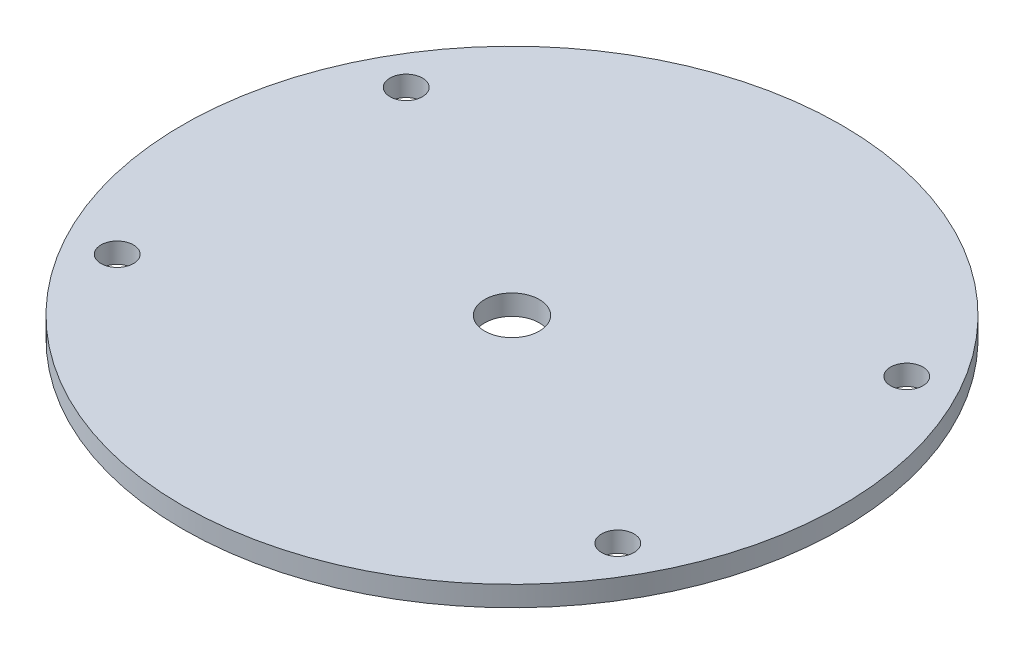
SolidWorks part; units mm, degrees
ref_plane "前视基准面" through (0, 0, 0) normal (0, 0, 1) x (1, 0, 0)
ref_plane "上视基准面" through (0, 0, 0) normal (0, 1, 0) x (1, 0, 0)
ref_plane "右视基准面" through (0, 0, 0) normal (1, 0, 0) x (0, 0, -1)
sketch "草图1" plane through (0, 0, 0) normal (0, 1, 0) x (1, 0, 0)
  line L0 (0, 0) -> (28.1458, -16.25) construction
  line L1 (0, 0) -> (32.5, 0) construction
  line L2 (0, 0) -> (0, -32.5) construction
  circle A0 centre (0, 0) radius 32.5
  circle A12 centre (24.6817, -14.25) radius 1.6
  circle A20 centre (-24.6817, -14.25) radius 1.6
  circle A21 centre (24.6817, 14.25) radius 1.6
  circle A22 centre (-24.6817, 14.25) radius 1.6
  circle A23 centre (0, 0) radius 2.7
  point P15 (0, 0)
  dimension "D1" = 30
  dimension "D2" = 65
  dimension "D6" = 3.2
  dimension "D7" = 4
extrude "凸台-拉伸1" add sketch "草图1" along normal blind 2
